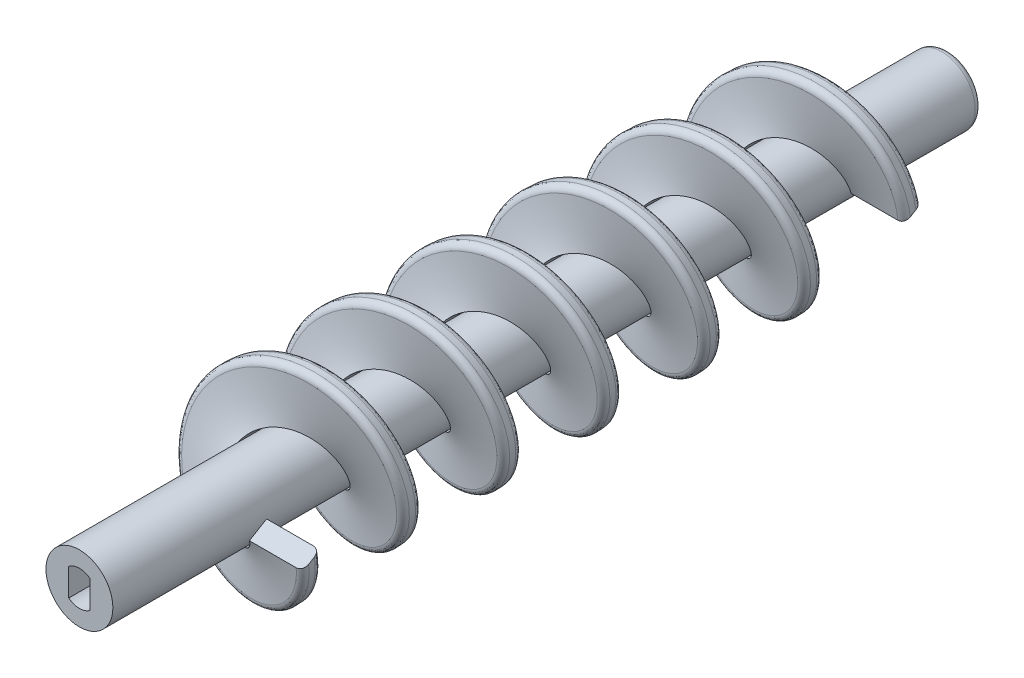
SolidWorks part; units mm, degrees
ref_plane "Front Plane" through (0, 0, 0) normal (0, 0, 1) x (1, 0, 0)
ref_plane "Top Plane" through (0, 0, 0) normal (0, 1, 0) x (1, 0, 0)
ref_plane "Right Plane" through (0, 0, 0) normal (1, 0, 0) x (0, 0, -1)
sketch "Sketch2" plane through (0, 0, 0) normal (0, 0, 1) x (1, 0, 0)
  circle A0 centre (0, 0) radius 5
  dimension "D1" = 10
extrude "Boss-Extrude1" add sketch "Sketch2" along normal mid plane 113
sketch "Sketch3" plane through (0, 0, -56.5) normal (0, 0, -1) x (-1, 0, 0)
  circle A0 centre (0, 0) radius 4
curve "Helix/Spiral1" pitch 15 height 90 radius 4 centre (0, 0, -56.5) axis (0, 0, 1) start towards (1, 0, 0)
ref_plane "Plane1" through (4, 0, -56.5) normal (0, 0.8587, 0.5125) x (1, 0, 0)
sketch "Sketch5" plane through (4, 0, -56.5) normal (0, 0.8587, 0.5125) x (1, 0, 0)
  line L1 (1, 0) -> (8, 0)
  line L2 (1, 0) -> (1, -3)
  line L3 (1, -3) -> (8, -3)
  line L4 (9, -1) -> (9, -2)
  arc A0 (8, -3) -> (9, -2) centre (8, -2) ccw
  arc A1 (8, 0) -> (9, -1) centre (8, -1) cw
  ellipse E0 centre (-4, 0) end of major axis (-9, 0) minor radius 2.5625 construction
  point P14 (9, 0)
  dimension "D3" = 1
  dimension "D1" = 8
  dimension "D2" = 3
sweep "Sweep1" add profiles "Sketch5" path "Helix/Spiral1"
sketch "Sketch6" plane through (0, 0, 56.5) normal (0, 0, 1) x (1, 0, 0)
  line L1 (-1.6, -2.0494) -> (1.6, -2.0494)
  line L2 (-1.6, -2.0494) -> (-1.6, 2.0494)
  line L3 (-1.6, 2.0494) -> (1.6, 2.0494)
  line L4 (1.6, -2.0494) -> (1.6, 2.0494)
  line L5 (-1.6, -2.0494) -> (1.6, 2.0494) construction
  line L6 (-1.6, 2.0494) -> (1.6, -2.0494) construction
  circle A0 centre (0, 0) radius 2.6
  dimension "D1" = 5.2
  dimension "D2" = 3.2
extrude "Cut-Extrude1" cut sketch "Sketch6" against normal blind 9 contours L3 A0 | L1 L4 L3 L2 | L1 A0 region at (0, 0, 56.5) region at (0, -2.2718, 56.5) region at (0, 2.2718, 56.5)
sketch "Sketch7" plane through (0, 0, -56.5) normal (0, 0, -1) x (-1, 0, 0)
  circle A0 centre (0, 0) radius 5
extrude "Boss-Extrude3" add sketch "Sketch7" along normal blind 17
fillet "Fillet1" radius 1 1 edges at (-5, 0, -73.5)
